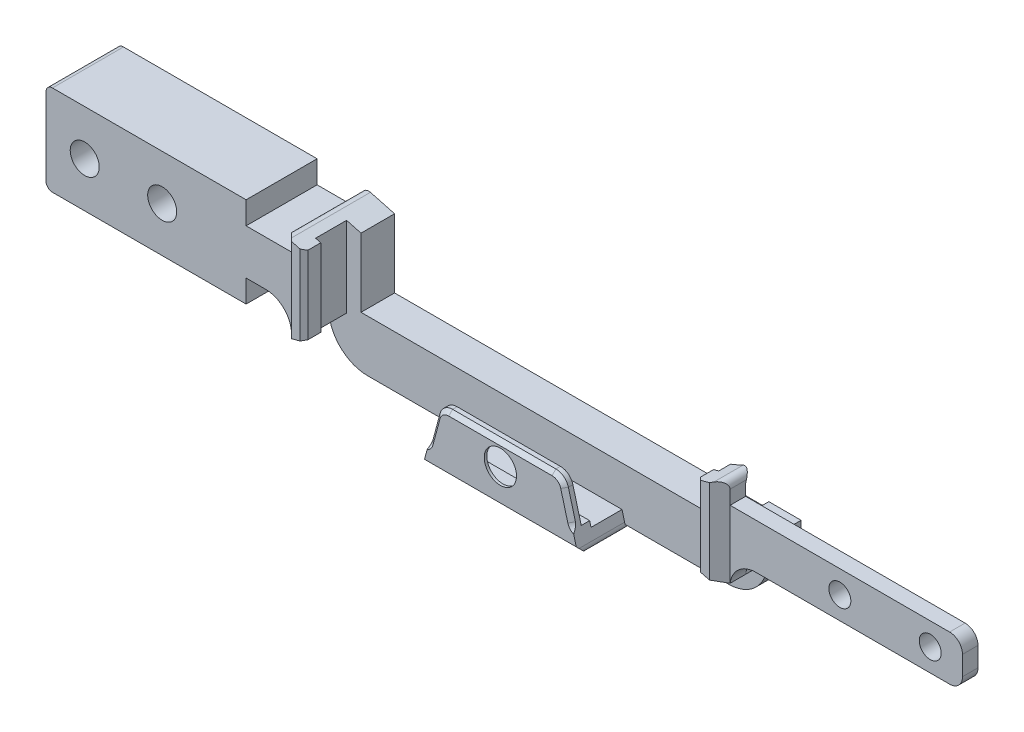
SolidWorks part; units mm, degrees
ref_plane "Ebene vorne" through (0, 0, 0) normal (0, 0, 1) x (1, 0, 0)
ref_plane "Ebene oben" through (0, 0, 0) normal (0, 1, 0) x (1, 0, 0)
ref_plane "Ebene rechts" through (0, 0, 0) normal (1, 0, 0) x (0, 0, -1)
sketch "Skizze1" plane through (0, 0, 2.3001) normal (0, 0, 1) x (1, 0, 0)
  line L0 (-27.9511, -4.5825) -> (-26.1511, -4.5825)
  line L1 (-26.1511, -4.5825) -> (-26.1511, 2.6565)
  line L2 (-26.1511, 2.6565) -> (-22.49, 2.6565)
  line L3 (-22.49, 2.6565) -> (-22.49, -4.5825)
  line L4 (-22.49, -4.5825) -> (-20.69, -4.5825)
  line L5 (-20.69, -4.5825) -> (-20.69, 2.6565)
  line L6 (-20.69, 2.6565) -> (-17.41, 2.6565)
  line L7 (-17.41, 2.6565) -> (-17.41, -4.5825)
  line L8 (-17.41, -4.5825) -> (-15.61, -4.5825)
  line L10 (-16.2652, 4.4565) -> (-27.9511, 4.4565)
  line L11 (-27.9511, 4.4565) -> (-27.9511, -4.5825)
  line L24 (-11.695, 4.4565) -> (-5.069, 4.4565)
  line L25 (-5.069, 4.4565) -> (-5.069, -4.5825)
  line L26 (-5.069, -4.5825) -> (-9.095, -4.5825)
  line L27 (-9.095, -4.5825) -> (-11.695, -4.1241)
  line L28 (-11.695, -4.1241) -> (-11.695, 0.2038)
  line L29 (-11.695, 0.2038) -> (-9.095, 0.9005)
  line L31 (-7.355, -0.8995) -> (-9.895, -0.8995)
  line L32 (-9.895, -0.8995) -> (-9.895, -2.7825)
  line L33 (-9.895, -2.7825) -> (-6.869, -2.7825)
  line L34 (-6.869, -2.7825) -> (-6.869, 2.6565)
  line L35 (-6.869, 2.6565) -> (-11.695, 2.6565)
  line L36 (-11.695, 2.6565) -> (-11.695, 4.4565)
  line L50 (1.259, 8.3935) -> (1.259, 4.4565)
  line L51 (1.259, 4.4565) -> (-1.154, 4.4565)
  line L52 (-1.154, 4.4565) -> (-1.154, 2.6565)
  line L53 (-1.154, 2.6565) -> (1.259, 2.6565)
  line L54 (1.259, 2.6565) -> (1.259, -4.5825)
  line L55 (1.259, -4.5825) -> (5.472, -4.5825)
  line L56 (5.472, -4.5825) -> (5.472, -2.7825)
  line L57 (5.472, -2.7825) -> (3.059, -2.7825)
  line L58 (3.059, -2.7825) -> (3.059, 2.6565)
  line L59 (3.059, 2.6565) -> (5.472, 2.6565)
  line L60 (5.472, 2.6565) -> (5.472, 4.4565)
  line L61 (5.472, 4.4565) -> (3.059, 4.4565)
  line L62 (3.059, 4.4565) -> (3.059, 8.3935)
  line L63 (3.059, 8.3935) -> (1.259, 8.3935)
  line L64 (-16.01, 0.6435) -> (-16.01, 1.6435) construction
  line L65 (-27.5511, 4.0565) -> (-27.5511, 3.0565) construction
  line L66 (-26.5511, -1.7695) -> (-26.5511, -0.7695) construction
  line L67 (-22.09, 1.6435) -> (-22.09, 0.6435) construction
  line L68 (-21.09, 0.6435) -> (-21.09, 1.6435) construction
  line L69 (-20.312, 3.0565) -> (-19.312, 3.0565) construction
  line L70 (-15.61, 2.6565) -> (-16.2652, 4.4565)
  line L71 (-24.138, 4.0565) -> (-25.138, 4.0565) construction
  line L72 (-27.5511, -4.1825) -> (-26.5511, -4.1825) construction
  line L73 (-17.01, 1.6435) -> (-17.01, 0.6435) construction
  line L74 (19.928, 8.2665) -> (19.928, -4.5825)
  line L75 (19.928, -4.5825) -> (21.728, -4.5825)
  line L76 (21.728, -4.5825) -> (21.728, 2.6565)
  line L77 (21.728, 2.6565) -> (25.8971, 2.6565)
  line L78 (25.8971, 2.6565) -> (25.8971, -4.5825)
  line L79 (25.8971, -4.5825) -> (27.6971, -4.5825)
  line L80 (27.6971, -4.5825) -> (27.6971, 2.6565)
  line L83 (27.0419, 4.4565) -> (21.728, 4.4565)
  line L84 (21.728, 4.4565) -> (21.728, 8.2665)
  line L85 (21.728, 8.2665) -> (19.928, 8.2665)
  line L86 (16.013, 2.6565) -> (12.057, 2.6565)
  line L87 (12.057, 2.6565) -> (11.187, 1.7865)
  line L88 (11.187, 1.7865) -> (11.187, -1.9125)
  line L89 (11.187, -1.9125) -> (12.057, -2.7825)
  line L90 (12.057, -2.7825) -> (16.013, -2.7825)
  line L91 (16.013, -2.7825) -> (16.013, -4.5825)
  line L92 (16.013, -4.5825) -> (11.155, -4.5825)
  line L93 (11.155, -4.5825) -> (9.387, -3.099)
  line L94 (9.387, -3.099) -> (9.387, 2.973)
  line L95 (9.387, 2.973) -> (11.155, 4.4565)
  line L96 (11.155, 4.4565) -> (16.013, 4.4565)
  line L97 (16.013, 4.4565) -> (16.013, 2.6565)
  line L98 (-0.754, 4.0565) -> (-0.754, 3.0565) construction
  line L99 (0.246, 4.0565) -> (-0.754, 4.0565) construction
  line L100 (1.659, 5.1995) -> (1.659, 4.1995) construction
  line L101 (2.659, 7.9935) -> (1.659, 7.9935) construction
  line L102 (2.659, 6.9935) -> (2.659, 7.9935) construction
  line L103 (5.072, 3.0565) -> (5.072, 4.0565) construction
  line L104 (4.072, 3.0565) -> (5.072, 3.0565) construction
  line L105 (2.659, 1.4055) -> (2.659, 2.4055) construction
  line L106 (5.072, -4.1825) -> (5.072, -3.1825) construction
  line L107 (5.072, -3.1825) -> (4.072, -3.1825) construction
  line L108 (1.659, -4.1825) -> (2.659, -4.1825) construction
  line L109 (9.787, 0.3735) -> (9.787, -0.6265) construction
  line L110 (10.787, -0.6265) -> (10.787, 0.3735) construction
  line L111 (-11.295, 4.0565) -> (-11.295, 3.0565) construction
  line L112 (-10.295, 4.0565) -> (-11.295, 4.0565) construction
  line L113 (14.613, 3.0565) -> (15.613, 3.0565) construction
  line L114 (15.613, 3.0565) -> (15.613, 4.0565) construction
  line L115 (13.2, 4.0565) -> (12.2, 4.0565) construction
  line L116 (12.2, -4.1825) -> (13.2, -4.1825) construction
  line L117 (20.328, -0.2615) -> (20.328, -1.2615) construction
  line L118 (21.328, -1.2615) -> (21.328, -0.2615) construction
  line L119 (22.741, 3.0565) -> (23.741, 3.0565) construction
  line L120 (26.2971, 1.7705) -> (26.2971, 0.7705) construction
  line L121 (27.2971, 0.7705) -> (27.2971, 1.7705) construction
  line L122 (23.741, 4.0565) -> (22.741, 4.0565) construction
  line L123 (21.328, 7.8665) -> (20.328, 7.8665) construction
  line L124 (21.328, 6.8665) -> (21.328, 7.8665) construction
  line L125 (27.6971, 2.6565) -> (27.0419, 4.4565)
  line L126 (20.328, -4.1825) -> (21.328, -4.1825) construction
  line L127 (-15.61, -4.5825) -> (-15.61, 2.6565)
  line L129 (-11.295, 3.0565) -> (-10.295, 3.0565) construction
  line L130 (-11.295, -0.1345) -> (-11.295, -1.1345) construction
  line L131 (-8.882, -4.1825) -> (-7.882, -4.1825) construction
  line L132 (-5.469, 3.0565) -> (-5.469, 4.0565) construction
  line L134 (-6.469, 1.6435) -> (-6.469, 0.6435) construction
  line L135 (-7.882, -3.1825) -> (-8.882, -3.1825) construction
  line L136 (-10.295, -1.1345) -> (-10.295, -0.1345) construction
  line L137 (-9.095, 0.9005) -> (-7.355, 0.9005)
  line L138 (-7.355, 0.9005) -> (-7.355, -0.8995)
  line L140 (-7.755, 0.5005) -> (-8.755, 0.5005) construction
  line L141 (-4.469, 4.8565) -> (-12.095, 4.8565)
  line L142 (-4.469, 4.8565) -> (-4.469, -5.1825)
  line L143 (-4.469, -5.1825) -> (-12.095, -5.1825)
  line L144 (-12.095, 4.8565) -> (-12.095, -5.1825)
  line L145 (-7.755, -0.4995) -> (-7.755, 0.5005) construction
  line L146 (-8.755, -0.4995) -> (-7.755, -0.4995) construction
  line L147 (-15.9151, 4.9565) -> (-28.4511, 4.9565)
  line L148 (-28.4511, 4.9565) -> (-28.4511, -5.0825)
  line L149 (-28.4511, -5.0825) -> (-25.6511, -5.0825)
  line L150 (-25.6511, -5.0825) -> (-25.6511, 2.1565)
  line L151 (-25.6511, 2.1565) -> (-22.99, 2.1565)
  line L152 (-22.99, 2.1565) -> (-22.99, -5.0825)
  line L153 (-22.99, -5.0825) -> (-20.19, -5.0825)
  line L154 (-20.19, -5.0825) -> (-20.19, 2.1565)
  line L155 (-20.19, 2.1565) -> (-17.91, 2.1565)
  line L156 (-17.91, 2.1565) -> (-17.91, -5.0825)
  line L157 (-17.91, -5.0825) -> (-15.11, -5.0825)
  line L158 (-15.11, -5.0825) -> (-15.11, 2.7447)
  line L159 (-15.11, 2.7447) -> (-15.9151, 4.9565)
  line L160 (5.972, 4.9565) -> (3.559, 4.9565)
  line L161 (3.559, 4.9565) -> (3.559, 8.8935)
  line L162 (3.559, 8.8935) -> (0.759, 8.8935)
  line L163 (0.759, 8.8935) -> (0.759, 4.9565)
  line L164 (0.759, 4.9565) -> (-1.654, 4.9565)
  line L165 (-1.654, 4.9565) -> (-1.654, 2.1565)
  line L166 (-1.654, 2.1565) -> (0.759, 2.1565)
  line L167 (0.759, 2.1565) -> (0.759, -5.0825)
  line L168 (0.759, -5.0825) -> (5.972, -5.0825)
  line L169 (5.972, -5.0825) -> (5.972, -2.2825)
  line L170 (5.972, -2.2825) -> (3.559, -2.2825)
  line L171 (3.559, -2.2825) -> (3.559, 2.1565)
  line L172 (3.559, 2.1565) -> (5.972, 2.1565)
  line L173 (5.972, 2.1565) -> (5.972, 4.9565)
  line L174 (10.973, 4.9565) -> (16.513, 4.9565)
  line L175 (16.513, 4.9565) -> (16.513, 2.1565)
  line L176 (16.513, 2.1565) -> (12.2641, 2.1565)
  line L177 (12.2641, 2.1565) -> (11.687, 1.5794)
  line L178 (11.687, 1.5794) -> (11.687, -1.7054)
  line L179 (11.687, -1.7054) -> (12.2641, -2.2825)
  line L180 (12.2641, -2.2825) -> (16.513, -2.2825)
  line L181 (16.513, -2.2825) -> (16.513, -5.0825)
  line L182 (16.513, -5.0825) -> (10.973, -5.0825)
  line L183 (10.973, -5.0825) -> (8.887, -3.3322)
  line L184 (8.887, -3.3322) -> (8.887, 3.2062)
  line L185 (8.887, 3.2062) -> (10.973, 4.9565)
  line L186 (27.322, 4.8565) -> (22.128, 4.8565)
  line L187 (22.128, 4.8565) -> (22.128, 8.6665)
  line L188 (22.128, 8.6665) -> (19.528, 8.6665)
  line L189 (19.528, 8.6665) -> (19.528, -4.9825)
  line L190 (19.528, -4.9825) -> (22.128, -4.9825)
  line L191 (22.128, -4.9825) -> (22.128, 2.2565)
  line L192 (22.128, 2.2565) -> (25.4971, 2.2565)
  line L193 (25.4971, 2.2565) -> (25.4971, -4.9825)
  line L194 (25.4971, -4.9825) -> (28.0971, -4.9825)
  line L195 (28.0971, -4.9825) -> (28.0971, 2.727)
  line L196 (28.0971, 2.727) -> (27.322, 4.8565)
  dimension "D1" = 0.4
  dimension "D2" = 0.4
  dimension "D3" = 0.4
  dimension "D4" = 0.4
  dimension "D5" = 0.4
  dimension "D7" = 0.4
  dimension "D8" = 0.4
  dimension "D9" = 0.4
  dimension "D10" = 0.4
  dimension "D11" = 0.4
  dimension "D12" = 0.4
  dimension "D13" = 0.4
  dimension "D14" = 0.4
  dimension "D15" = 0.4
  dimension "D16" = 0.4
  dimension "D17" = 0.4
  dimension "D18" = 0.4
  dimension "D19" = 0.4
  dimension "D20" = 0.4
  dimension "D21" = 0.4
  dimension "D22" = 0.4
  dimension "D23" = 0.4
  dimension "D24" = 0.4
  dimension "D25" = 0.4
  dimension "D26" = 0.4
  dimension "D27" = 130
  dimension "D28" = 135
  dimension "D29" = 0.4
  dimension "D30" = 0.4
  dimension "D31" = 0.4
  dimension "D32" = 0.4
  dimension "D33" = 0.4
  dimension "D34" = 0.4
  dimension "D35" = 0.4
  dimension "D36" = 0.4
  dimension "D37" = 0.4
  dimension "D38" = 0.4
  dimension "D39" = 20
  dimension "D40" = 0.4
  dimension "D6" = 0.4
  dimension "D41" = 200
  dimension "D42" = 0.4
  dimension "D43" = 0.4
  dimension "D44" = 0.4
  dimension "D45" = 0.4
  dimension "D46" = 0.4
  dimension "D47" = 0.4
  dimension "D48" = 0.4
  dimension "D49" = 0.4
  dimension "D50" = 0.4
  dimension "D51" = 105
  dimension "D52" = 0.4
  dimension "D53" = 0.4
  dimension "D54" = 0.4
  dimension "D55" = 2.6
  dimension "D56" = 0.4
  dimension "D58" = 0.6
  dimension "D59" = 0.4
  dimension "D57" = 10
  dimension "D64" = 2.6
  dimension "D65" = 0.6
  dimension "D60" = 0.5
  dimension "D61" = 0.5
  dimension "D62" = 0.5
  dimension "D63" = 0.4
extrude "Aufsatz-Linear austragen1" add sketch "Skizze1" along normal blind 1.5
sketch "Skizze2" plane through (0, 0, 3.8001) normal (0, 0, 1) x (1, 0, 0)
  line L0 (30.9874, 8.5) -> (30.9874, -8.5) construction
  line L1 (27.0001, -12.4873) -> (-27.0001, -12.4873) construction
  line L2 (-30.9874, -8.5) -> (-30.9874, 8.5) construction
  line L3 (-27.0001, 12.4873) -> (27.0001, 12.4873) construction
  line L4 (30.9874, 8.5) -> (30.9874, -8.5) construction
  line L5 (27.0001, -12.4873) -> (-27.0001, -12.4873) construction
  line L6 (-30.9874, -8.5) -> (-30.9874, 8.5) construction
  line L7 (-27.0001, 12.4873) -> (27.0001, 12.4873) construction
  line L8 (-27.0001, 15.4873) -> (27.0001, 15.4873)
  line L9 (33.9874, 8.5) -> (33.9874, -8.5)
  line L10 (27.0001, -15.4873) -> (-27.0001, -15.4873)
  line L11 (-33.9874, -8.5) -> (-33.9874, 8.5)
  arc A0 (30.9874, 8.5) -> (27.0001, 12.4873) centre (27.0001, 8.5) ccw construction
  arc A1 (27.0001, -12.4873) -> (30.9874, -8.5) centre (27.0001, -8.5) ccw construction
  arc A2 (-30.9874, -8.5) -> (-27.0001, -12.4873) centre (-27.0001, -8.5) ccw construction
  arc A3 (-27.0001, 12.4873) -> (-30.9874, 8.5) centre (-27.0001, 8.5) ccw construction
  arc A4 (30.9874, 8.5) -> (27.0001, 12.4873) centre (27.0001, 8.5) ccw construction
  arc A5 (27.0001, -12.4873) -> (30.9874, -8.5) centre (27.0001, -8.5) ccw construction
  arc A6 (-30.9874, -8.5) -> (-27.0001, -12.4873) centre (-27.0001, -8.5) ccw construction
  arc A7 (-27.0001, 12.4873) -> (-30.9874, 8.5) centre (-27.0001, 8.5) ccw construction
  circle A8 centre (0, -9.017) radius 2.5
  arc A9 (0.7218, -9.017) -> (-0.7218, -9.017) centre (0, -9.017) ccw construction
  arc A10 (0.7218, -9.017) -> (-0.7218, -9.017) centre (0, -9.017) ccw construction
  arc A11 (33.9874, 8.5) -> (27.0001, 15.4873) centre (27.0001, 8.5) ccw
  arc A12 (27.0001, -15.4873) -> (33.9874, -8.5) centre (27.0001, -8.5) ccw
  arc A13 (-33.9874, -8.5) -> (-27.0001, -15.4873) centre (-27.0001, -8.5) ccw
  arc A14 (-27.0001, 15.4873) -> (-33.9874, 8.5) centre (-27.0001, 8.5) ccw
  dimension "D1" = 5
  dimension "D2" = 3
extrude "Aufsatz-Linear austragen2" add sketch "Skizze2" along normal blind 0.4
sketch "Skizze3" plane through (0, 0, 3.8001) normal (0, 0, -1) x (-1, 0, 0)
  line L12 (-27.225, 11.925) -> (27.225, 11.925)
  line L13 (-27.225, -12.725) -> (27.225, -12.725)
  line L14 (-31.225, -8.725) -> (-31.225, 8.725)
  line L15 (-27.225, 12.725) -> (27.225, 12.725)
  line L16 (31.225, -8.725) -> (31.225, 8.725)
  line L17 (-31.225, -12.725) -> (31.225, 12.725) construction
  line L18 (-31.225, 12.725) -> (31.225, -12.725) construction
  line L19 (30.425, -8.725) -> (30.425, 8.725)
  line L20 (-27.225, -11.925) -> (27.225, -11.925)
  line L21 (-30.425, -8.725) -> (-30.425, 8.725)
  arc A12 (27.225, 12.725) -> (31.225, 8.725) centre (27.225, 8.725) cw
  arc A13 (27.225, -12.725) -> (31.225, -8.725) centre (27.225, -8.725) ccw
  arc A14 (-31.225, -8.725) -> (-27.225, -12.725) centre (-27.225, -8.725) ccw
  arc A15 (-31.225, 8.725) -> (-27.225, 12.725) centre (-27.225, 8.725) cw
  arc A16 (27.225, 11.925) -> (30.425, 8.725) centre (27.225, 8.725) cw
  arc A17 (27.225, -11.925) -> (30.425, -8.725) centre (27.225, -8.725) ccw
  arc A18 (-30.425, -8.725) -> (-27.225, -11.925) centre (-27.225, -8.725) ccw
  arc A19 (-30.425, 8.725) -> (-27.225, 11.925) centre (-27.225, 8.725) cw
  point P0 (0, 0)
  dimension "D3" = 4
  dimension "D1" = 62.45
  dimension "D2" = 25.45
  dimension "D4" = 0.8
extrude "Aufsatz-Linear austragen3" add sketch "Skizze3" along normal blind 2.2
sketch "Skizze10" plane through (0, 0, 3.8001) normal (0, 0, -1) x (-1, 0, 0)
  line L0 (27.225, 12.725) -> (-27.225, 12.725) construction
  line L1 (27.225, 12.725) -> (-27.225, 12.725)
  line L4 (27.0001, 15.4873) -> (-27.0001, 15.4873)
  line L5 (-33.9874, 8.5) -> (-33.9874, -8.5)
  line L6 (-27.0001, -15.4873) -> (27.0001, -15.4873)
  line L7 (33.9874, -8.5) -> (33.9874, 8.5)
  line L8 (27.0001, 15.4873) -> (-27.0001, 15.4873)
  line L9 (-33.9874, 8.5) -> (-33.9874, -8.5)
  line L10 (-27.0001, -15.4873) -> (27.0001, -15.4873)
  line L11 (33.9874, -8.5) -> (33.9874, 8.5)
  line L14 (31.225, -8.725) -> (31.225, 8.725)
  line L15 (31.225, -8.725) -> (31.225, 8.725)
  line L16 (-27.225, -12.725) -> (27.225, -12.725)
  line L17 (-27.225, -12.725) -> (27.225, -12.725)
  line L22 (-31.225, 8.725) -> (-31.225, -8.725)
  line L23 (-31.225, 8.725) -> (-31.225, -8.725)
  line L24 (27.225, 12.725) -> (-27.225, 12.725)
  line L25 (27.225, 12.725) -> (-27.225, 12.725)
  arc A1 (27.225, -12.725) -> (31.225, -8.725) centre (27.225, -8.725) ccw
  arc A4 (33.9874, 8.5) -> (27.0001, 15.4873) centre (27.0001, 8.5) ccw
  arc A5 (-27.0001, 15.4873) -> (-33.9874, 8.5) centre (-27.0001, 8.5) ccw
  arc A6 (-33.9874, -8.5) -> (-27.0001, -15.4873) centre (-27.0001, -8.5) ccw
  arc A7 (27.0001, -15.4873) -> (33.9874, -8.5) centre (27.0001, -8.5) ccw
  arc A8 (33.9874, 8.5) -> (27.0001, 15.4873) centre (27.0001, 8.5) ccw
  arc A9 (-27.0001, 15.4873) -> (-33.9874, 8.5) centre (-27.0001, 8.5) ccw
  arc A10 (-33.9874, -8.5) -> (-27.0001, -15.4873) centre (-27.0001, -8.5) ccw
  arc A11 (27.0001, -15.4873) -> (33.9874, -8.5) centre (27.0001, -8.5) ccw
  arc A15 (27.225, -12.725) -> (31.225, -8.725) centre (27.225, -8.725) ccw
  arc A20 (-31.225, -8.725) -> (-27.225, -12.725) centre (-27.225, -8.725) ccw
  arc A21 (-31.225, -8.725) -> (-27.225, -12.725) centre (-27.225, -8.725) ccw
  arc A22 (-27.225, 12.725) -> (-31.225, 8.725) centre (-27.225, 8.725) ccw
  arc A23 (-27.225, 12.725) -> (-31.225, 8.725) centre (-27.225, 8.725) ccw
  arc A24 (31.225, 8.725) -> (27.225, 12.725) centre (27.225, 8.725) ccw
  arc A25 (31.225, 8.725) -> (27.225, 12.725) centre (27.225, 8.725) ccw
  dimension "D1" = 0
  dimension "D2" = 0
extrude "Aufsatz-Linear austragen14" add sketch "Skizze10" along normal blind 7 contours A8 L8 A9 L9 A10 L10 A11 L11 | L15 A25 L25 A23 L23 A21 L17 A15
sketch "Skizze11" plane through (0, 0, 0) normal (1, 0, 0) x (0, 0, -1)
  line L0 (3.1999, 12.725) -> (-1.6001, 12.725) construction
  line L1 (3.1999, 12.725) -> (-0.1001, 12.725)
  line L2 (-0.1001, 12.725) -> (3.1999, 12.725)
  line L3 (3.1999, 12.725) -> (-0.1001, 13.4264)
  line L4 (-0.1001, 13.4264) -> (-0.1001, 12.725)
  line L5 (-0.1001, 13.4264) -> (3.1999, 12.725)
  line L6 (3.1999, 12.725) -> (-1.6001, 12.725)
  dimension "D1" = 12
  dimension "D2" = 1.5
sketch "Skizze12" plane through (0, 0, -3.1999) normal (0, 0, -1) x (-1, 0, 0)
  line L4 (31.225, -8.725) -> (31.225, 8.725)
  line L16 (31.225, -8.725) -> (31.225, 8.725)
  line L20 (-27.225, -12.725) -> (27.225, -12.725)
  line L22 (-27.225, -12.725) -> (27.225, -12.725)
  line L24 (-31.225, 8.725) -> (-31.225, -8.725)
  line L25 (-31.225, 8.725) -> (-31.225, -8.725)
  line L26 (27.225, 12.725) -> (-27.225, 12.725)
  line L27 (27.225, 12.725) -> (-27.225, 12.725)
  arc A4 (27.225, -12.725) -> (31.225, -8.725) centre (27.225, -8.725) ccw
  arc A16 (27.225, -12.725) -> (31.225, -8.725) centre (27.225, -8.725) ccw
  arc A20 (-31.225, -8.725) -> (-27.225, -12.725) centre (-27.225, -8.725) ccw
  arc A22 (-31.225, -8.725) -> (-27.225, -12.725) centre (-27.225, -8.725) ccw
  arc A24 (-27.225, 12.725) -> (-31.225, 8.725) centre (-27.225, 8.725) ccw
  arc A25 (-27.225, 12.725) -> (-31.225, 8.725) centre (-27.225, 8.725) ccw
  arc A26 (31.225, 8.725) -> (27.225, 12.725) centre (27.225, 8.725) ccw
  arc A27 (31.225, 8.725) -> (27.225, 12.725) centre (27.225, 8.725) ccw
  dimension "D1" = 0
sketch "Skizze14" plane through (0, 0, 3.8001) normal (0, 0, -1) x (-1, 0, 0)
  line L4 (27.225, 11.925) -> (-27.225, 11.925)
  line L5 (-30.425, 8.725) -> (-30.425, -8.725)
  line L6 (-27.225, -11.925) -> (27.225, -11.925)
  line L7 (30.425, -8.725) -> (30.425, 8.725)
  line L8 (27.225, 11.925) -> (-27.225, 11.925)
  line L9 (-30.425, 8.725) -> (-30.425, -8.725)
  line L10 (-27.225, -11.925) -> (27.225, -11.925)
  line L11 (30.425, -8.725) -> (30.425, 8.725)
  line L12 (4.469, -5.1825) -> (12.095, -5.1825)
  line L13 (4.469, 4.8565) -> (4.469, -5.1825)
  line L14 (12.095, 4.8565) -> (4.469, 4.8565)
  line L15 (12.095, -5.1825) -> (12.095, 4.8565)
  line L16 (4.469, -5.1825) -> (12.095, -5.1825)
  line L17 (4.469, 4.8565) -> (4.469, -5.1825)
  line L18 (12.095, 4.8565) -> (4.469, 4.8565)
  line L19 (12.095, -5.1825) -> (12.095, 4.8565)
  line L21 (15.9151, 4.9565) -> (15.11, 2.7447)
  line L22 (28.4511, 4.9565) -> (15.9151, 4.9565)
  line L23 (28.4511, -5.0825) -> (28.4511, 4.9565)
  line L24 (25.6511, -5.0825) -> (28.4511, -5.0825)
  line L25 (25.6511, 2.1565) -> (25.6511, -5.0825)
  line L26 (22.99, 2.1565) -> (25.6511, 2.1565)
  line L27 (22.99, -5.0825) -> (22.99, 2.1565)
  line L28 (20.19, -5.0825) -> (22.99, -5.0825)
  line L29 (20.19, 2.1565) -> (20.19, -5.0825)
  line L30 (17.91, 2.1565) -> (20.19, 2.1565)
  line L31 (17.91, -5.0825) -> (17.91, 2.1565)
  line L32 (15.11, -5.0825) -> (17.91, -5.0825)
  line L33 (15.11, 2.7447) -> (15.11, -5.0825)
  line L34 (15.9151, 4.9565) -> (15.11, 2.7447)
  line L35 (28.4511, 4.9565) -> (15.9151, 4.9565)
  line L36 (28.4511, -5.0825) -> (28.4511, 4.9565)
  line L37 (25.6511, -5.0825) -> (28.4511, -5.0825)
  line L38 (25.6511, 2.1565) -> (25.6511, -5.0825)
  line L39 (22.99, 2.1565) -> (25.6511, 2.1565)
  line L40 (22.99, -5.0825) -> (22.99, 2.1565)
  line L41 (20.19, -5.0825) -> (22.99, -5.0825)
  line L42 (20.19, 2.1565) -> (20.19, -5.0825)
  line L43 (17.91, 2.1565) -> (20.19, 2.1565)
  line L44 (17.91, -5.0825) -> (17.91, 2.1565)
  line L45 (15.11, -5.0825) -> (17.91, -5.0825)
  line L46 (15.11, 2.7447) -> (15.11, -5.0825)
  line L53 (-27.322, 4.8565) -> (-28.0971, 2.727)
  line L54 (-8.887, 3.2062) -> (-10.973, 4.9565)
  line L55 (-8.887, -3.3322) -> (-8.887, 3.2062)
  line L56 (-5.972, 4.9565) -> (-5.972, 2.1565)
  line L57 (-3.559, 4.9565) -> (-5.972, 4.9565)
  line L58 (-3.559, 8.8935) -> (-3.559, 4.9565)
  line L59 (-0.759, 8.8935) -> (-3.559, 8.8935)
  line L60 (-0.759, 4.9565) -> (-0.759, 8.8935)
  line L61 (1.654, 4.9565) -> (-0.759, 4.9565)
  line L62 (1.654, 2.1565) -> (1.654, 4.9565)
  line L63 (-0.759, 2.1565) -> (1.654, 2.1565)
  line L64 (-0.759, -5.0825) -> (-0.759, 2.1565)
  line L65 (-5.972, -5.0825) -> (-0.759, -5.0825)
  line L66 (-5.972, -2.2825) -> (-5.972, -5.0825)
  line L67 (-3.559, -2.2825) -> (-5.972, -2.2825)
  line L68 (-3.559, 2.1565) -> (-3.559, -2.2825)
  line L69 (-5.972, 2.1565) -> (-3.559, 2.1565)
  line L70 (-5.972, 4.9565) -> (-5.972, 2.1565)
  line L71 (-3.559, 4.9565) -> (-5.972, 4.9565)
  line L72 (-3.559, 8.8935) -> (-3.559, 4.9565)
  line L73 (-0.759, 8.8935) -> (-3.559, 8.8935)
  line L74 (-0.759, 4.9565) -> (-0.759, 8.8935)
  line L75 (1.654, 4.9565) -> (-0.759, 4.9565)
  line L76 (1.654, 2.1565) -> (1.654, 4.9565)
  line L77 (-0.759, 2.1565) -> (1.654, 2.1565)
  line L78 (-0.759, -5.0825) -> (-0.759, 2.1565)
  line L79 (-5.972, -5.0825) -> (-0.759, -5.0825)
  line L80 (-5.972, -2.2825) -> (-5.972, -5.0825)
  line L81 (-3.559, -2.2825) -> (-5.972, -2.2825)
  line L82 (-3.559, 2.1565) -> (-3.559, -2.2825)
  line L83 (-5.972, 2.1565) -> (-3.559, 2.1565)
  line L84 (-10.973, -5.0825) -> (-8.887, -3.3322)
  line L85 (-16.513, -5.0825) -> (-10.973, -5.0825)
  line L86 (-16.513, -2.2825) -> (-16.513, -5.0825)
  line L87 (-12.2641, -2.2825) -> (-16.513, -2.2825)
  line L88 (-11.687, -1.7054) -> (-12.2641, -2.2825)
  line L89 (-11.687, 1.5794) -> (-11.687, -1.7054)
  line L90 (-12.2641, 2.1565) -> (-11.687, 1.5794)
  line L91 (-16.513, 2.1565) -> (-12.2641, 2.1565)
  line L92 (-16.513, 4.9565) -> (-16.513, 2.1565)
  line L93 (-10.973, 4.9565) -> (-16.513, 4.9565)
  line L94 (-8.887, 3.2062) -> (-10.973, 4.9565)
  line L95 (-8.887, -3.3322) -> (-8.887, 3.2062)
  line L96 (-10.973, -5.0825) -> (-8.887, -3.3322)
  line L97 (-16.513, -5.0825) -> (-10.973, -5.0825)
  line L98 (-16.513, -2.2825) -> (-16.513, -5.0825)
  line L99 (-12.2641, -2.2825) -> (-16.513, -2.2825)
  line L100 (-11.687, -1.7054) -> (-12.2641, -2.2825)
  line L101 (-11.687, 1.5794) -> (-11.687, -1.7054)
  line L102 (-12.2641, 2.1565) -> (-11.687, 1.5794)
  line L103 (-16.513, 2.1565) -> (-12.2641, 2.1565)
  line L104 (-16.513, 4.9565) -> (-16.513, 2.1565)
  line L105 (-10.973, 4.9565) -> (-16.513, 4.9565)
  line L106 (-22.128, 4.8565) -> (-27.322, 4.8565)
  line L107 (-22.128, 8.6665) -> (-22.128, 4.8565)
  line L108 (-19.528, 8.6665) -> (-22.128, 8.6665)
  line L109 (-19.528, -4.9825) -> (-19.528, 8.6665)
  line L110 (-22.128, -4.9825) -> (-19.528, -4.9825)
  line L111 (-22.128, 2.2565) -> (-22.128, -4.9825)
  line L112 (-25.4971, 2.2565) -> (-22.128, 2.2565)
  line L113 (-25.4971, -4.9825) -> (-25.4971, 2.2565)
  line L114 (-28.0971, -4.9825) -> (-25.4971, -4.9825)
  line L115 (-28.0971, 2.727) -> (-28.0971, -4.9825)
  line L116 (-27.322, 4.8565) -> (-28.0971, 2.727)
  line L117 (-22.128, 4.8565) -> (-27.322, 4.8565)
  line L118 (-22.128, 8.6665) -> (-22.128, 4.8565)
  line L119 (-19.528, 8.6665) -> (-22.128, 8.6665)
  line L120 (-19.528, -4.9825) -> (-19.528, 8.6665)
  line L121 (-22.128, -4.9825) -> (-19.528, -4.9825)
  line L122 (-22.128, 2.2565) -> (-22.128, -4.9825)
  line L123 (-25.4971, 2.2565) -> (-22.128, 2.2565)
  line L124 (-25.4971, -4.9825) -> (-25.4971, 2.2565)
  line L125 (-28.0971, -4.9825) -> (-25.4971, -4.9825)
  line L126 (-28.0971, 2.727) -> (-28.0971, -4.9825)
  circle A1 centre (0, -9.017) radius 2.5
  circle A2 centre (0, -9.017) radius 2.5
  arc A4 (30.425, 8.725) -> (27.225, 11.925) centre (27.225, 8.725) ccw
  arc A5 (-27.225, 11.925) -> (-30.425, 8.725) centre (-27.225, 8.725) ccw
  arc A6 (-30.425, -8.725) -> (-27.225, -11.925) centre (-27.225, -8.725) ccw
  arc A7 (27.225, -11.925) -> (30.425, -8.725) centre (27.225, -8.725) ccw
  arc A8 (30.425, 8.725) -> (27.225, 11.925) centre (27.225, 8.725) ccw
  arc A9 (-27.225, 11.925) -> (-30.425, 8.725) centre (-27.225, 8.725) ccw
  arc A10 (-30.425, -8.725) -> (-27.225, -11.925) centre (-27.225, -8.725) ccw
  arc A11 (27.225, -11.925) -> (30.425, -8.725) centre (27.225, -8.725) ccw
  dimension "D1" = 0
  dimension "D2" = 0
  dimension "D3" = 0
  dimension "D4" = 0
  dimension "D5" = 0
  dimension "D6" = 0
  dimension "D7" = 0
extrude "Aufsatz-Linear austragen15" add sketch "Skizze14" along normal blind 0.9
sketch "Skizze13" plane through (33.9874, 0, 0) normal (1, 0, 0) x (0, 0, -1)
  line L0 (3.1999, 8.5) -> (3.1999, -8.5) construction
  line L1 (1.7999, -5.5) -> (3.9999, -5.5)
  line L2 (-0.2001, -3.5) -> (-0.2001, 3.5)
  line L3 (1.7999, 5.5) -> (3.9999, 5.5)
  line L4 (5.9999, -3.5) -> (5.9999, 3.5)
  line L5 (-0.2001, -5.5) -> (5.9999, 5.5) construction
  line L6 (-0.2001, 5.5) -> (5.9999, -5.5) construction
  arc A0 (3.9999, -5.5) -> (5.9999, -3.5) centre (3.9999, -3.5) ccw
  arc A1 (1.7999, -5.5) -> (-0.2001, -3.5) centre (1.7999, -3.5) cw
  arc A2 (1.7999, 5.5) -> (-0.2001, 3.5) centre (1.7999, 3.5) ccw
  arc A3 (5.9999, 3.5) -> (3.9999, 5.5) centre (3.9999, 3.5) ccw
  point P0 (2.8999, 0)
  point P18 (0, 0)
  dimension "D1" = 2
  dimension "D2" = 11
  dimension "D3" = 6.2
  dimension "D4" = 0.3
extrude "Schnitt-Linear austragen1" cut sketch "Skizze13" against normal blind 5 contours L2 A2 L3 A3 L4 A0 L1 A1
sketch "Skizze15" plane through (0, 0, 2.9001) normal (0, 0, -1) x (-1, 0, 0)
  line L0 (-5, -9.017) -> (5, -9.017) construction
  line L1 (-5, -6.109) -> (5, -6.109)
  line L2 (-5, -11.925) -> (5, -11.925)
  line L3 (-27.225, -11.925) -> (27.225, -11.925) construction
  arc A0 (-5, -6.109) -> (-5, -11.925) centre (-5, -9.017) ccw
  arc A1 (5, -11.925) -> (5, -6.109) centre (5, -9.017) ccw
  point P2 (0, -9.017)
  dimension "D1" = 10
extrude "Schnitt-Linear austragen2" cut sketch "Skizze15" against normal blind 0.9
chamfer "Fase1" distance 1.6 angle 45 8 edges at (-31.9408, -13.4408, 4.2001) (0, -15.4873, 4.2001) (-33.9874, 0, 4.2001) (31.9408, -13.4408, 4.2001) (-31.9408, 13.4408, 4.2001) (33.9874, 0, 4.2001) (0, 15.4873, 4.2001) (31.9408, 13.4408, 4.2001)
sketch "Skizze16" plane through (0, 0, 3.8001) normal (0, 0, -1) x (-1, 0, 0)
  line L0 (26.1511, -4.5825) -> (27.9511, -4.5825) construction
  line L1 (27.9511, -4.5825) -> (27.9511, 4.4565) construction
  line L2 (27.9511, 4.4565) -> (16.2652, 4.4565) construction
  line L3 (16.2652, 4.4565) -> (15.61, 2.6565) construction
  line L4 (15.61, 2.6565) -> (15.61, -4.5825) construction
  line L5 (15.61, -4.5825) -> (17.41, -4.5825) construction
  line L6 (17.41, -4.5825) -> (17.41, 2.6565) construction
  line L7 (17.41, 2.6565) -> (20.69, 2.6565) construction
  line L8 (20.69, 2.6565) -> (20.69, -4.5825) construction
  line L9 (20.69, -4.5825) -> (22.49, -4.5825) construction
  line L10 (22.49, -4.5825) -> (22.49, 2.6565) construction
  line L11 (22.49, 2.6565) -> (26.1511, 2.6565) construction
  line L12 (26.1511, 2.6565) -> (26.1511, -4.5825) construction
  line L13 (7.355, 0.9005) -> (7.355, -0.8995) construction
  line L14 (7.355, -0.8995) -> (9.895, -0.8995) construction
  line L15 (9.895, -0.8995) -> (9.895, -2.7825) construction
  line L16 (9.895, -2.7825) -> (6.869, -2.7825) construction
  line L17 (6.869, -2.7825) -> (6.869, 2.6565) construction
  line L18 (6.869, 2.6565) -> (11.695, 2.6565) construction
  line L19 (11.695, 2.6565) -> (11.695, 4.4565) construction
  line L20 (11.695, 4.4565) -> (5.069, 4.4565) construction
  line L21 (5.069, 4.4565) -> (5.069, -4.5825) construction
  line L22 (5.069, -4.5825) -> (9.095, -4.5825) construction
  line L23 (9.095, -4.5825) -> (11.695, -4.1241) construction
  line L24 (11.695, -4.1241) -> (11.695, 0.2038) construction
  line L25 (11.695, 0.2038) -> (9.095, 0.9005) construction
  line L26 (9.095, 0.9005) -> (7.355, 0.9005) construction
  line L27 (-1.259, 4.4565) -> (-1.259, 8.3935) construction
  line L28 (-1.259, 8.3935) -> (-3.059, 8.3935) construction
  line L29 (-3.059, 8.3935) -> (-3.059, 4.4565) construction
  line L30 (-3.059, 4.4565) -> (-5.472, 4.4565) construction
  line L31 (-5.472, 4.4565) -> (-5.472, 2.6565) construction
  line L32 (-5.472, 2.6565) -> (-3.059, 2.6565) construction
  line L33 (-3.059, 2.6565) -> (-3.059, -2.7825) construction
  line L34 (-3.059, -2.7825) -> (-5.472, -2.7825) construction
  line L35 (-5.472, -2.7825) -> (-5.472, -4.5825) construction
  line L36 (-5.472, -4.5825) -> (-1.259, -4.5825) construction
  line L37 (-1.259, -4.5825) -> (-1.259, 2.6565) construction
  line L38 (-1.259, 2.6565) -> (1.154, 2.6565) construction
  line L39 (1.154, 2.6565) -> (1.154, 4.4565) construction
  line L40 (1.154, 4.4565) -> (-1.259, 4.4565) construction
  line L41 (-11.155, 4.4565) -> (-16.013, 4.4565) construction
  line L42 (-16.013, 4.4565) -> (-16.013, 2.6565) construction
  line L43 (-16.013, 2.6565) -> (-12.057, 2.6565) construction
  line L44 (-12.057, 2.6565) -> (-11.187, 1.7865) construction
  line L45 (-11.187, 1.7865) -> (-11.187, -1.9125) construction
  line L46 (-11.187, -1.9125) -> (-12.057, -2.7825) construction
  line L47 (-12.057, -2.7825) -> (-16.013, -2.7825) construction
  line L48 (-16.013, -2.7825) -> (-16.013, -4.5825) construction
  line L49 (-16.013, -4.5825) -> (-11.155, -4.5825) construction
  line L50 (-11.155, -4.5825) -> (-9.387, -3.099) construction
  line L51 (-9.387, -3.099) -> (-9.387, 2.973) construction
  line L52 (-9.387, 2.973) -> (-11.155, 4.4565) construction
  line L53 (-19.928, -4.5825) -> (-19.928, 8.2665) construction
  line L54 (-19.928, 8.2665) -> (-21.728, 8.2665) construction
  line L55 (-21.728, 8.2665) -> (-21.728, 4.4565) construction
  line L56 (-21.728, 4.4565) -> (-27.0419, 4.4565) construction
  line L57 (-27.0419, 4.4565) -> (-27.6971, 2.6565) construction
  line L58 (-27.6971, 2.6565) -> (-27.6971, -4.5825) construction
  line L59 (-27.6971, -4.5825) -> (-25.8971, -4.5825) construction
  line L60 (-25.8971, -4.5825) -> (-25.8971, 2.6565) construction
  line L61 (-25.8971, 2.6565) -> (-21.728, 2.6565) construction
  line L62 (-21.728, 2.6565) -> (-21.728, -4.5825) construction
  line L63 (-21.728, -4.5825) -> (-19.928, -4.5825) construction
  line L64 (26.1511, -4.5825) -> (27.9511, -4.5825)
  line L65 (27.9511, -4.5825) -> (27.9511, 4.4565)
  line L66 (27.9511, 4.4565) -> (16.2652, 4.4565)
  line L67 (16.2652, 4.4565) -> (15.61, 2.6565)
  line L68 (15.61, 2.6565) -> (15.61, -4.5825)
  line L69 (15.61, -4.5825) -> (17.41, -4.5825)
  line L70 (17.41, -4.5825) -> (17.41, 2.6565)
  line L71 (17.41, 2.6565) -> (20.69, 2.6565)
  line L72 (20.69, 2.6565) -> (20.69, -4.5825)
  line L73 (20.69, -4.5825) -> (22.49, -4.5825)
  line L74 (22.49, -4.5825) -> (22.49, 2.6565)
  line L75 (22.49, 2.6565) -> (26.1511, 2.6565)
  line L76 (26.1511, 2.6565) -> (26.1511, -4.5825)
  line L77 (7.355, 0.9005) -> (7.355, -0.8995)
  line L78 (7.355, -0.8995) -> (9.895, -0.8995)
  line L79 (9.895, -0.8995) -> (9.895, -2.7825)
  line L80 (9.895, -2.7825) -> (6.869, -2.7825)
  line L81 (6.869, -2.7825) -> (6.869, 2.6565)
  line L82 (6.869, 2.6565) -> (11.695, 2.6565)
  line L83 (11.695, 2.6565) -> (11.695, 4.4565)
  line L84 (11.695, 4.4565) -> (5.069, 4.4565)
  line L85 (5.069, 4.4565) -> (5.069, -4.5825)
  line L86 (5.069, -4.5825) -> (9.095, -4.5825)
  line L87 (9.095, -4.5825) -> (11.695, -4.1241)
  line L88 (11.695, -4.1241) -> (11.695, 0.2038)
  line L89 (11.695, 0.2038) -> (9.095, 0.9005)
  line L90 (9.095, 0.9005) -> (7.355, 0.9005)
  line L91 (-1.259, 4.4565) -> (-1.259, 8.3935)
  line L92 (-1.259, 8.3935) -> (-3.059, 8.3935)
  line L93 (-3.059, 8.3935) -> (-3.059, 4.4565)
  line L94 (-3.059, 4.4565) -> (-5.472, 4.4565)
  line L95 (-5.472, 4.4565) -> (-5.472, 2.6565)
  line L96 (-5.472, 2.6565) -> (-3.059, 2.6565)
  line L97 (-3.059, 2.6565) -> (-3.059, -2.7825)
  line L98 (-3.059, -2.7825) -> (-5.472, -2.7825)
  line L99 (-5.472, -2.7825) -> (-5.472, -4.5825)
  line L100 (-5.472, -4.5825) -> (-1.259, -4.5825)
  line L101 (-1.259, -4.5825) -> (-1.259, 2.6565)
  line L102 (-1.259, 2.6565) -> (1.154, 2.6565)
  line L103 (1.154, 2.6565) -> (1.154, 4.4565)
  line L104 (1.154, 4.4565) -> (-1.259, 4.4565)
  line L105 (-11.155, 4.4565) -> (-16.013, 4.4565)
  line L106 (-16.013, 4.4565) -> (-16.013, 2.6565)
  line L107 (-16.013, 2.6565) -> (-12.057, 2.6565)
  line L108 (-12.057, 2.6565) -> (-11.187, 1.7865)
  line L109 (-11.187, 1.7865) -> (-11.187, -1.9125)
  line L110 (-11.187, -1.9125) -> (-12.057, -2.7825)
  line L111 (-12.057, -2.7825) -> (-16.013, -2.7825)
  line L112 (-16.013, -2.7825) -> (-16.013, -4.5825)
  line L113 (-16.013, -4.5825) -> (-11.155, -4.5825)
  line L114 (-11.155, -4.5825) -> (-9.387, -3.099)
  line L115 (-9.387, -3.099) -> (-9.387, 2.973)
  line L116 (-9.387, 2.973) -> (-11.155, 4.4565)
  line L117 (-19.928, -4.5825) -> (-19.928, 8.2665)
  line L118 (-19.928, 8.2665) -> (-21.728, 8.2665)
  line L119 (-21.728, 8.2665) -> (-21.728, 4.4565)
  line L120 (-21.728, 4.4565) -> (-27.0419, 4.4565)
  line L121 (-27.0419, 4.4565) -> (-27.6971, 2.6565)
  line L122 (-27.6971, 2.6565) -> (-27.6971, -4.5825)
  line L123 (-27.6971, -4.5825) -> (-25.8971, -4.5825)
  line L124 (-25.8971, -4.5825) -> (-25.8971, 2.6565)
  line L125 (-25.8971, 2.6565) -> (-21.728, 2.6565)
  line L126 (-21.728, 2.6565) -> (-21.728, -4.5825)
  line L127 (-21.728, -4.5825) -> (-19.928, -4.5825)
extrude "Cut_Letters_optional" [suppressed] cut sketch "Skizze16" against normal through all contours L117 L118 L119 L120 L121 L122 L123 L124 L125 L126 L127 | L105 L106 L107 L108 L109 L110 L111 L112 L113 L114 L115 L116 | L91 L92 L93 L94 L95 L96 L97 L98 L99 L100 L101 L102 L103 L104 | L77 L78 L79 L80 L81 L82 L83 L84 L85 L86 L87 L88 L89 L90 | L64 L65 L66 L67 L68 L69 L70 L71 L72 L73 L74 L75 L76
sketch "Skizze17" plane through (0, 0, 4.2001) normal (0, 0, 1) x (1, 0, 0)
  circle A1 centre (0, -9.017) radius 2.5
  circle A2 centre (0, -9.017) radius 2.5
  circle A3 centre (0, -9.017) radius 2.5
  circle A4 centre (0, -9.017) radius 2.5
  circle A5 centre (0, -9.017) radius 2.5
  circle A6 centre (0, -9.017) radius 2.5
  circle A7 centre (0, -9.017) radius 2.5
  circle A8 centre (0, -9.017) radius 2.5
  circle A9 centre (0, -9.017) radius 2.5
  circle A10 centre (0, -9.017) radius 2.5
  dimension "D1" = 0
  dimension "D2" = 0
  dimension "D3" = 0
  dimension "D4" = 0
  dimension "D5" = 0
extrude "Letters_single" [suppressed] add sketch "Skizze17" against normal blind 0.3 separate body
sketch "Skizze18" plane through (0, 0, 4.2001) normal (0, 0, 1) x (1, 0, 0)
  line L0 (-27.225, 11.925) -> (27.225, 11.925) construction
  line L1 (-27.225, 11.925) -> (27.225, 11.925)
  line L2 (-5, -6.109) -> (5, -6.109) construction
  line L3 (-30.425, -8.725) -> (-30.425, 8.725) construction
  line L4 (30.425, 8.725) -> (30.425, -8.725) construction
  line L5 (-5, -6.109) -> (5, -6.109) construction
  line L6 (-30.425, -8.725) -> (-30.425, 8.725)
  line L7 (30.425, 8.725) -> (30.425, -8.725)
  line L8 (-27.225, -11.925) -> (-11.9943, -11.925)
  line L9 (27.225, -11.925) -> (11.9943, -11.925)
  line L10 (9.9319, -7.0914) -> (11.0284, -11.1838)
  line L11 (8, -5.609) -> (-8, -5.609)
  line L12 (-9.9319, -7.0914) -> (-11.0284, -11.1838)
  arc A0 (-5, -6.109) -> (-5, -11.925) centre (-5, -9.017) ccw construction
  arc A1 (5, -11.925) -> (5, -6.109) centre (5, -9.017) ccw construction
  arc A2 (27.225, -11.925) -> (30.425, -8.725) centre (27.225, -8.725) ccw construction
  arc A3 (-30.425, -8.725) -> (-27.225, -11.925) centre (-27.225, -8.725) ccw construction
  arc A4 (-27.225, 11.925) -> (-30.425, 8.725) centre (-27.225, 8.725) ccw construction
  arc A5 (30.425, 8.725) -> (27.225, 11.925) centre (27.225, 8.725) ccw construction
  arc A6 (-5, -6.109) -> (-5, -11.925) centre (-5, -9.017) ccw construction
  arc A7 (5, -11.925) -> (5, -6.109) centre (5, -9.017) ccw construction
  arc A8 (27.225, -11.925) -> (30.425, -8.725) centre (27.225, -8.725) ccw
  arc A9 (-30.425, -8.725) -> (-27.225, -11.925) centre (-27.225, -8.725) ccw
  arc A10 (-27.225, 11.925) -> (-30.425, 8.725) centre (-27.225, 8.725) ccw
  arc A11 (30.425, 8.725) -> (27.225, 11.925) centre (27.225, 8.725) ccw
  arc A12 (-11.9943, -11.925) -> (-11.0284, -11.1838) centre (-11.9943, -10.925) ccw
  arc A13 (-9.9319, -7.0914) -> (-8, -5.609) centre (-8, -7.609) cw
  arc A14 (8, -5.609) -> (9.9319, -7.0914) centre (8, -7.609) cw
  arc A15 (11.9943, -11.925) -> (11.0284, -11.1838) centre (11.9943, -10.925) cw
  point P30 (0, -5.609)
  point P31 (0, -6.109)
  dimension "D4" = 1
  dimension "D5" = 2
  dimension "D1" = 1
  dimension "D2" = 30
  dimension "D3" = 16
extrude "Schnitt-Linear austragen4" cut sketch "Skizze18" against normal through all
chamfer "Fase2" distance 0.6 angle 45 16 edges at (0, -5.609, 4.2001) (9.2175, -6.0223, 4.2001) (-9.2175, -6.0223, 4.2001) (10.4801, -9.1376, 4.2001) (-10.4801, -9.1376, 4.2001) (11.3856, -11.7184, 4.2001) (-11.3856, -11.7184, 4.2001) (19.6097, -11.925, 4.2001) (-19.6097, -11.925, 4.2001) (29.4877, -10.9877, 4.2001) (-29.4877, -10.9877, 4.2001) (30.425, 0, 4.2001) (-30.425, 0, 4.2001) (29.4877, 10.9877, 4.2001) (-29.4877, 10.9877, 4.2001) (0, 11.925, 4.2001)
sketch "Skizze19" plane through (0, 0, 4.2001) normal (0, 0, 1) x (1, 0, 0)
  line L0 (-35.9874, 17.4873) -> (-35.9874, 6.0127)
  line L1 (-35.9874, 6.0127) -> (-28.425, 3.9863)
  line L2 (-28.425, 3.9863) -> (-28.425, -6.961)
  line L3 (-28.425, -6.961) -> (-35.9874, -8.9873)
  line L4 (-35.9874, -8.9873) -> (-35.9874, -17.4873)
  line L5 (-35.9874, -17.4873) -> (-12.7174, -17.4873)
  line L6 (-12.7174, -17.4873) -> (-9.5347, -5.609)
  line L7 (-9.5347, -5.609) -> (9.5347, -5.609)
  line L8 (9.5347, -5.609) -> (12.7174, -17.4873)
  line L9 (12.7174, -17.4873) -> (35.9874, -17.4873)
  line L10 (35.9874, -17.4873) -> (35.9874, -8.9873)
  line L11 (35.9874, -8.9873) -> (28.425, -6.961)
  line L12 (28.425, -6.961) -> (28.425, 3.9863)
  line L13 (28.425, 3.9863) -> (35.9874, 6.0127)
  line L14 (35.9874, 6.0127) -> (35.9874, 17.4873)
  line L15 (35.9874, 17.4873) -> (-35.9874, 17.4873)
  line L16 (-11.0284, -11.1838) -> (-9.9319, -7.0914) construction
  line L17 (9.9319, -7.0914) -> (11.0284, -11.1838) construction
  line L18 (-8, -5.609) -> (8, -5.609) construction
  line L19 (33.9874, 8.5) -> (33.9874, -8.5) construction
  line L20 (-27.0001, 15.4873) -> (27.0001, 15.4873) construction
  line L21 (27.0001, -15.4873) -> (-27.0001, -15.4873) construction
  line L22 (-30.425, 8.725) -> (-30.425, -8.725) construction
  point P3 (0, 0)
  point P16 (35.9874, 9.0653)
  point P17 (24.5694, 2.2178)
  point P18 (41.768, 5.1297)
  point P20 (-38.4011, 5.1297)
  point P27 (41.2799, 4.8928)
  point P31 (-24.2543, -4.1262)
  point P32 (40.7526, 11.0924)
  point P33 (0, 0)
  point P40 (0, 0)
  dimension "D1" = 2
  dimension "D2" = 2
  dimension "D3" = 2
  dimension "D4" = 2
  dimension "D5" = 15
  dimension "D6" = 6.5
extrude "Schnitt-Linear austragen5" cut sketch "Skizze19" against normal through all
sketch "Skizze20" plane through (0, 0, -3.1999) normal (0, 0, -1) x (-1, 0, 0)
  line L0 (33.9874, 5.4768) -> (33.9874, -14.4873)
  line L1 (33.9874, -8.4514) -> (33.9874, 5.4768) construction
  line L2 (33.9874, -14.4873) -> (-33.9874, -14.4873)
  line L3 (-33.9874, -14.4873) -> (-33.9874, -5.5)
  line L4 (-33.9874, -5.5) -> (-28.9874, -5.5)
  line L5 (-28.9874, -5.5) -> (-28.9874, -6.4873)
  line L6 (-28.9874, -6.4873) -> (28.9874, -6.4873)
  line L7 (28.9874, -6.4873) -> (28.9874, 4.137)
  line L8 (28.9874, 4.137) -> (33.9874, 5.4768)
  line L9 (-12.1815, -15.4873) -> (12.1815, -15.4873) construction
  line L11 (33.9874, 5.4768) -> (31.225, 4.7366) construction
  point P4 (28.1931, -10.3249)
  point P17 (33.9874, 3.5695)
  point P18 (0, 0)
  point P22 (33.9874, 2.5127)
  point P23 (33.9874, 5.5371)
  dimension "D1" = 8
  dimension "D2" = 5
  dimension "D3" = 5
  dimension "D4" = 1
extrude "Aufsatz-Linear austragen16" add sketch "Skizze20" along normal blind 5.2
fillet "Verrundung1" radius 6 2 edges at (33.9874, -14.4873, -5.7999) (-33.9874, -14.4873, -5.7999)
fillet "Verrundung2" radius 1 2 edges at (-12.1815, -15.4873, -0.2999) (12.1815, -15.4873, -0.2999)
chamfer "Fase3" distance 1 angle 45 1 edges at (0, -14.4873, -3.1999)
ref_plane "Ebene1" through (0, 0, 2.6001) normal (0, 0, 1) x (1, 0, 0)
sketch "Skizze21" plane through (0, 0, 2.6001) normal (0, 0, 1) x (1, 0, 0)
  line L0 (-33.9874, -8.4514) -> (-33.9874, 5.4768) construction
  line L1 (-33.9874, 2.0127) -> (-69.9874, 2.0127)
  line L2 (-33.9874, 2.0127) -> (-33.9874, -4.9873)
  line L3 (-33.9874, -4.9873) -> (-69.9874, -4.9873)
  line L4 (-69.9874, 2.0127) -> (-69.9874, -4.9873)
  line L5 (33.9874, 2.0127) -> (69.9874, 2.0127)
  line L6 (33.9874, 2.0127) -> (33.9874, -4.9873)
  line L7 (33.9874, -4.9873) -> (69.9874, -4.9873)
  line L8 (69.9874, 2.0127) -> (69.9874, -4.9873)
  line L9 (33.9874, 5.4768) -> (33.9874, -8.4514) construction
  point P10 (0, 0)
  point P15 (-33.9874, -1.4873)
  point P16 (-33.9874, -1.4873)
  point P19 (56.7827, 2.0127)
  dimension "D1" = 36
  dimension "D2" = 7
extrude "Aufsatz-Linear austragen17" add sketch "Skizze21" along normal up to surface (2.4 mm away)
fillet "Verrundung3" radius 4 2 edges at (-33.9874, -4.9873, 1.4001) (33.9874, -4.9873, 1.4001)
fillet "Verrundung4" radius 1 2 edges at (-33.9874, 5.4768, -2.8999) (33.9874, 5.4768, 0.552)
sketch "Skizze23" plane through (0, 0, 0.2001) normal (0, 0, -1) x (-1, 0, 0)
  line L4 (69.9874, 2.0127) -> (33.9874, 2.0127)
  line L5 (33.9874, 2.0127) -> (33.9874, -8.4514)
  line L6 (37.9513, -4.9873) -> (69.9874, -4.9873)
  line L7 (69.9874, -4.9873) -> (69.9874, 2.0127)
  line L8 (69.9874, 2.0127) -> (33.9874, 2.0127)
  line L10 (37.9513, -4.9873) -> (69.9874, -4.9873)
  line L11 (69.9874, -4.9873) -> (69.9874, 2.0127)
  line L12 (33.9874, 2.0127) -> (33.9874, -8.4514)
  arc A1 (37.9513, -4.9873) -> (33.9874, -8.4514) centre (37.9513, -8.9873) ccw
  arc A2 (37.9513, -4.9873) -> (33.9874, -8.4514) centre (37.9513, -8.9873) ccw
  dimension "D1" = 0
extrude "Aufsatz-Linear austragen18" add sketch "Skizze23" along normal up to surface (8.6 mm away) up to face at (-2.997, -5.3317, -8.3999)
sketch "Skizze24" plane through (0, 0, -8.3999) normal (0, 0, -1) x (-1, 0, 0)
  line L0 (28.9874, 4.137) -> (28.9874, -6.4873) construction
  line L1 (40.9874, -8.4873) -> (71.9874, -8.4873)
  line L2 (40.9874, -8.4873) -> (40.9874, 5.5127)
  line L3 (40.9874, 5.5127) -> (71.9874, 5.5127)
  line L4 (71.9874, -8.4873) -> (71.9874, 5.5127)
  line L5 (40.9874, -8.4873) -> (71.9874, 5.5127) construction
  line L6 (40.9874, 5.5127) -> (71.9874, -8.4873) construction
  line L7 (69.9874, 2.0127) -> (69.9874, -4.9873) construction
  point P0 (56.4874, -1.4873)
  point P9 (69.9874, -1.4873)
  dimension "D1" = 12
  dimension "D2" = 2
  dimension "D3" = 14
extrude "Aufsatz-Linear austragen19" add sketch "Skizze24" against normal up to surface (11 mm away) contours L2 L1 L4 L3 up to face at (-49.0501, -2.7313, 2.6001)
sketch "Skizze25" plane through (0, 0, -8.3999) normal (0, 0, -1) x (-1, 0, 0)
  line L0 (71.9874, -8.4873) -> (71.9874, 5.5127) construction
  point P0 (65.9874, -1.4873)
  point P1 (53.9874, -1.4873)
  point P2 (0, 0)
  point P5 (71.9874, -1.4873)
  dimension "D1" = 12
  dimension "D2" = 6
hole_wizard "Formsenkung für M4 Linsensenkschraube mit Schlitz1" positions "Skizze26" profile "Skizze27" countersink size "M4" standard "DIN" end condition through all
sketch "Skizze26" plane through (0, 0, -8.3999) normal (0, 0, -1) x (-1, 0, 0)
  point P0 (53.9874, -1.4873)
  point P3 (65.9874, -1.4873)
sketch "Skizze27" plane through (-53.9874, -1.4873, -8.3999) normal (1, 0, 0) x (0, 1, 0)
  line L0 (0, 0) -> (0, 12.7477)
  line L1 (0, 12.7477) -> (2.25, 12.7477)
  line L2 (2.25, 12.7477) -> (2.25, 2.45)
  line L3 (2.25, 2.45) -> (4.7, 0)
  line L5 (4.7, 0) -> (0, 0)
  line L6 (-2.25, 2.45) -> (-4.7, 0) construction
  line L11 (0, -6.35) -> (0, 107.95) construction
  dimension "Bohrerdurchmesser" = 4.5
  dimension "Bohrungstiefe" = 12.7477
  dimension "Senkdurchmesser (Oben)" = 9.4
  dimension "Senkwinkel (Oben)" = 90
fillet "Verrundung7" radius 1 2 edges at (-71.9874, -8.4873, -2.8999) (-71.9874, 5.5127, -2.8999)
sketch "Skizze29" plane through (0, 0, 0.2001) normal (0, 0, -1) x (-1, 0, 0)
  line L0 (-69.9874, -4.9873) -> (-69.9874, 2.0127) construction
  point P0 (-64.9874, -1.4873)
  point P1 (-50.9874, -1.4873)
  point P2 (0, 0)
  point P3 (-69.9874, -1.4873)
  point P4 (0, 0)
  dimension "D1" = 5
  dimension "D2" = 14
hole_wizard "Ø3.4 (3.4) Durchmesser Bohrung1" positions "Skizze30" profile "Skizze31" hole size "Ø3.4" standard "DIN" end condition through all
sketch "Skizze30" plane through (0, 0, 0.2001) normal (0, 0, -1) x (-1, 0, 0)
  point P0 (-50.9874, -1.4873)
  point P3 (-64.9874, -1.4873)
sketch "Skizze31" plane through (50.9874, -1.4873, 0.2001) normal (1, 0, 0) x (0, 1, 0)
  line L0 (0, 0) -> (0, 4.1477)
  line L1 (0, 4.1477) -> (1.7, 4.1477)
  line L2 (1.7, 4.1477) -> (1.7, 0)
  line L5 (1.7, 0) -> (0, 0)
  line L11 (0, -6.35) -> (0, 107.95) construction
  dimension "Bohrerdurchmesser" = 3.4
  dimension "Bohrungstiefe" = 4.1477
fillet "Verrundung8" radius 2 2 edges at (69.9874, -4.9873, 1.4001) (69.9874, 2.0127, 1.4001)
equation "\"D2@Skizze1\"=\"D1@Skizze1\""
equation "\"D3@Skizze1\"=\"D1@Skizze1\""
equation "\"D4@Skizze1\"=\"D1@Skizze1\""
equation "\"D5@Skizze1\"=\"D1@Skizze1\""
equation "\"D7@Skizze1\"=\"D1@Skizze1\""
equation "\"D8@Skizze1\"=\"D1@Skizze1\""
equation "\"D9@Skizze1\"=\"D1@Skizze1\""
equation "\"D11@Skizze1\"=\"D10@Skizze1\""
equation "\"D12@Skizze1\"=\"D10@Skizze1\""
equation "\"D13@Skizze1\"=\"D10@Skizze1\""
equation "\"D14@Skizze1\"=\"D10@Skizze1\""
equation "\"D15@Skizze1\"=\"D10@Skizze1\""
equation "\"D16@Skizze1\"=\"D10@Skizze1\""
equation "\"D17@Skizze1\"=\"D10@Skizze1\""
equation "\"D18@Skizze1\"=\"D10@Skizze1\""
equation "\"D20@Skizze1\"=\"D10@Skizze1\""
equation "\"D22@Skizze1\"=\"D21@Skizze1\""
equation "\"D23@Skizze1\"=\"D21@Skizze1\""
equation "\"D24@Skizze1\"=\"D21@Skizze1\""
equation "\"D25@Skizze1\"=\"D21@Skizze1\""
equation "\"D26@Skizze1\"=\"D21@Skizze1\""
equation "\"D33@Skizze1\"=\"D31@Skizze1\""
equation "\"D34@Skizze1\"=\"D31@Skizze1\""
equation "\"D35@Skizze1\"=\"D31@Skizze1\""
equation "\"D37@Skizze1\"=\"D31@Skizze1\""
equation "\"D38@Skizze1\"=\"D31@Skizze1\""
equation "\"D40@Skizze1\"=\"D31@Skizze1\""
equation "\"D32@Skizze1\"=\"D31@Skizze1\""
equation "\"D6@Skizze1\"=\"D1@Skizze1\""
equation "\"D43@Skizze1\"=\"D42@Skizze1\""
equation "\"D44@Skizze1\"=\"D42@Skizze1\""
equation "\"D45@Skizze1\"=\"D44@Skizze1\""
equation "\"D46@Skizze1\"=\"D42@Skizze1\""
equation "\"D47@Skizze1\"=\"D42@Skizze1\""
equation "\"D48@Skizze1\"=\"D42@Skizze1\""
equation "\"D49@Skizze1\"=\"D42@Skizze1\""
equation "\"D50@Skizze1\"=\"D42@Skizze1\""
equation "\"D54@Skizze1\"=\"D42@Skizze1\""
equation "\"D19@Skizze1\"=\"D10@Skizze1\""
